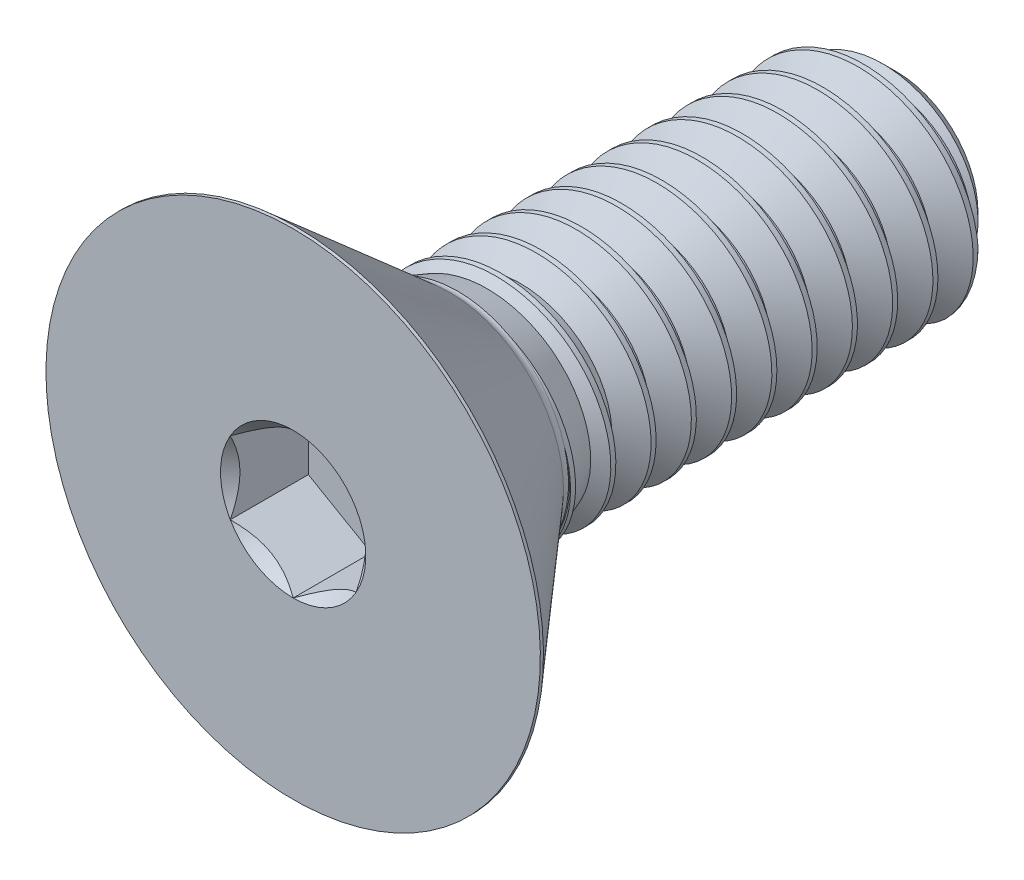
SolidWorks part; units mm, degrees
ref_plane "Front Plane" through (0, 0, 0) normal (0, 0, 1) x (1, 0, 0)
ref_plane "Top Plane" through (0, 0, 0) normal (0, 1, 0) x (1, 0, 0)
ref_plane "Right Plane" through (0, 0, 0) normal (1, 0, 0) x (0, 0, -1)
sketch "Sketch1" plane through (0, 0, 0) normal (1, 0, 0) x (0, 0, -1)
  line L0 (-4.7625, 0) -> (4.7625, 0) construction
  line L1 (-4.7625, 0) -> (-4.7625, 3.8989)
  line L2 (-4.7625, 3.8989) -> (-4.7132, 3.8989)
  line L3 (-4.7132, 3.8989) -> (-2.2987, 1.8)
  line L4 (-4.7132, -3.8989) -> (-2.2987, -1.8)
  line L5 (4.7625, 0) -> (4.7625, 1.7526)
  line L6 (4.7625, 1.7526) -> (-2.2987, 1.7526)
  line L7 (4.2862, 1.7526) -> (4.7625, 1.2764)
  line L8 (4.7228, 1.8213) -> (5.0403, 1.2714) construction
  line L9 (5.0403, 1.2714) -> (5.3578, 1.8213) construction
  line L10 (5.3578, 1.8213) -> (4.7228, 1.8213) construction
  line L11 (4.7427, 1.787) -> (5.338, 1.787)
  line L12 (5.338, 1.787) -> (5.08, 1.3402)
  line L13 (5.08, 1.3402) -> (5.0006, 1.3402)
  line L14 (5.0006, 1.3402) -> (4.7427, 1.787)
  line L15 (5.0403, 1.3402) -> (5.0403, 1.2714) construction
  line L16 (4.7625, 1.7526) -> (5.3181, 1.7526) construction
  line L17 (5.0403, 1.8213) -> (5.0403, 1.7526) construction
  line L18 (4.7625, -1.7526) -> (-2.2987, -1.7526)
  arc A0 (-2.2987, 1.8) -> (-2.172, 1.7526) centre (-2.172, 1.9458) ccw
  point P2 (0, 0)
  point P23 (-3.5306, 0)
  point P27 (5.0403, 1.787)
  point P30 (3.81, -1.7526)
  point P34 (-4.7132, -3.8989)
  dimension "Length" = 9.525
  dimension "Head Height" = 2.4638
  dimension "Head Diameter" = 7.7978
  dimension "Countersink Angle" = 82
  dimension "Thread Diameter" = 3.5052
  dimension "D2" = 0.0493
  dimension "Pitch" = 0.635
  dimension "D4" = 0.0794
  dimension "D3" = 45
  dimension "D5" = 0.4763
  dimension "D6" = 1.2319
  dimension "D1" = 0.9525
sketch "Sketch2" plane through (0, 0, 0) normal (0, 0, 1) x (1, 0, 0)
  line L1 (0, 1.1457) -> (-0.9922, 0.5728)
  line L2 (-0.9922, 0.5728) -> (-0.9922, -0.5728)
  line L3 (-0.9922, -0.5728) -> (0, -1.1457)
  line L4 (0, -1.1457) -> (0.9922, -0.5728)
  line L5 (0.9922, -0.5728) -> (0.9922, 0.5728)
  line L6 (0.9922, 0.5728) -> (0, 1.1457)
  circle A0 centre (0, 0) radius 0.9922 construction
  dimension "Drive Size" = 1.9844
sketch "Sketch11" plane through (0, 0, 0) normal (1, 0, 0) x (0, 0, -1)
  line L0 (-4.7132, 3.8989) -> (-2.2987, 1.8) construction
  line L1 (-4.7625, 0) -> (-4.7625, 3.8989) construction
  line L2 (-4.7132, 3.8989) -> (-2.2987, 1.8)
  line L3 (-4.7625, 0) -> (-4.7625, 3.8989)
  line L4 (-4.7625, 3.8989) -> (-4.7132, 3.8989) construction
  line L5 (-4.7625, 3.8989) -> (-4.7132, 3.8989)
  line L6 (-2.172, 1.7526) -> (4.2862, 1.7526)
  line L7 (4.2862, 1.7526) -> (4.7625, 1.2764)
  line L8 (4.7625, 1.2764) -> (4.7625, 0)
  line L9 (4.7625, 0) -> (-4.7625, 0)
  arc A0 (-2.2987, 1.8) -> (-2.172, 1.7526) centre (-2.172, 1.9458) ccw construction
  arc A1 (-2.2987, 1.8) -> (-2.172, 1.7526) centre (-2.172, 1.9458) ccw
revolve "Revolve1" add sketch "Sketch11" angle 360 about L9
sketch "Sketch9" plane through (0, 0, 4.7625) normal (0, 0, 1) x (1, 0, 0)
  line L0 (0.9922, -0.5728) -> (0.9922, 0.5728) construction
  line L1 (0, -1.1457) -> (0.9922, -0.5728) construction
  line L2 (-0.9922, -0.5728) -> (0, -1.1457) construction
  line L3 (-0.9922, 0.5728) -> (-0.9922, -0.5728) construction
  line L4 (0, 1.1457) -> (-0.9922, 0.5728) construction
  line L5 (0.9922, 0.5728) -> (0, 1.1457) construction
  line L6 (0.9922, -0.5728) -> (0.9922, 0.5728)
  line L7 (0, -1.1457) -> (0.9922, -0.5728)
  line L8 (-0.9922, -0.5728) -> (0, -1.1457)
  line L9 (-0.9922, 0.5728) -> (-0.9922, -0.5728)
  line L10 (0, 1.1457) -> (-0.9922, 0.5728)
  line L11 (0.9922, 0.5728) -> (0, 1.1457)
sketch "Sketch10" plane through (0, 0, 4.7625) normal (0, 0, 1) x (1, 0, 0)
  circle A0 centre (0, 0) radius 1.1457
extrude "Cut-Extrude2" cut sketch "Sketch10" against normal up to vertex (1.2319 mm away) draft 45 up to point (0, 0, 3.5306)
extrude "Cut-Extrude1" cut sketch "Sketch9" against normal up to vertex (1.2319 mm away) up to point (0, 0, 3.5306)
ref_plane "Plane1" through (0, 0, 2.172) normal (0, 0, 1) x (1, 0, 0)
split "Split1" trim tools "Plane1" bodies to split 111 resulting bodies 105 106
sketch "Sketch3" plane through (0, 0, -4.7625) normal (0, 0, -1) x (-1, 0, 0)
  circle A0 centre (0, 0) radius 1.7526 construction
  circle A1 centre (0, 0) radius 1.7526
curve "Helix/Spiral1" pitch 0.635 height 9.525 turns 15
sketch "Sketch4" plane through (0, 0, 0) normal (1, 0, 0) x (0, 0, -1)
  line L0 (4.7427, 1.787) -> (5.338, 1.787) construction
  line L1 (5.0006, 1.3402) -> (4.7427, 1.787) construction
  line L2 (5.08, 1.3402) -> (5.0006, 1.3402) construction
  line L3 (5.338, 1.787) -> (5.08, 1.3402) construction
  line L4 (4.7427, 1.787) -> (5.338, 1.787)
  line L5 (5.0006, 1.3402) -> (4.7427, 1.787)
  line L6 (5.08, 1.3402) -> (5.0006, 1.3402)
  line L7 (5.338, 1.787) -> (5.08, 1.3402)
sweep "Cut-Sweep1" cut profiles "Sketch4" path "Helix/Spiral1" align with end faces yes
sketch "Sketch7" plane through (0, 0, 2.172) normal (0, 0, 1) x (1, 0, 0)
  circle A0 centre (0, 0) radius 1.7526
extrude "Boss-Extrude2" add sketch "Sketch7" against normal up to next (6.9345 mm away) draft 20
equation "\"D2@Sketch1\"=\"Head Height@Sketch1\"/50"
equation "\"D4@Sketch1\" = \"Pitch@Sketch1\" / 8"
equation "\"D5@Sketch1\"=\"Pitch@Sketch1\"*0.75"
equation "\"D4@Helix/Spiral1\"=\"Pitch@Sketch1\""
equation "\"D3@Helix/Spiral1\"=\"Length@Sketch1\""
equation "\"D6@Sketch1\"=\"Head Height@Sketch1\"/2"
equation "\"D1@Sketch1\"=\"Pitch@Sketch1\"*1.5"
